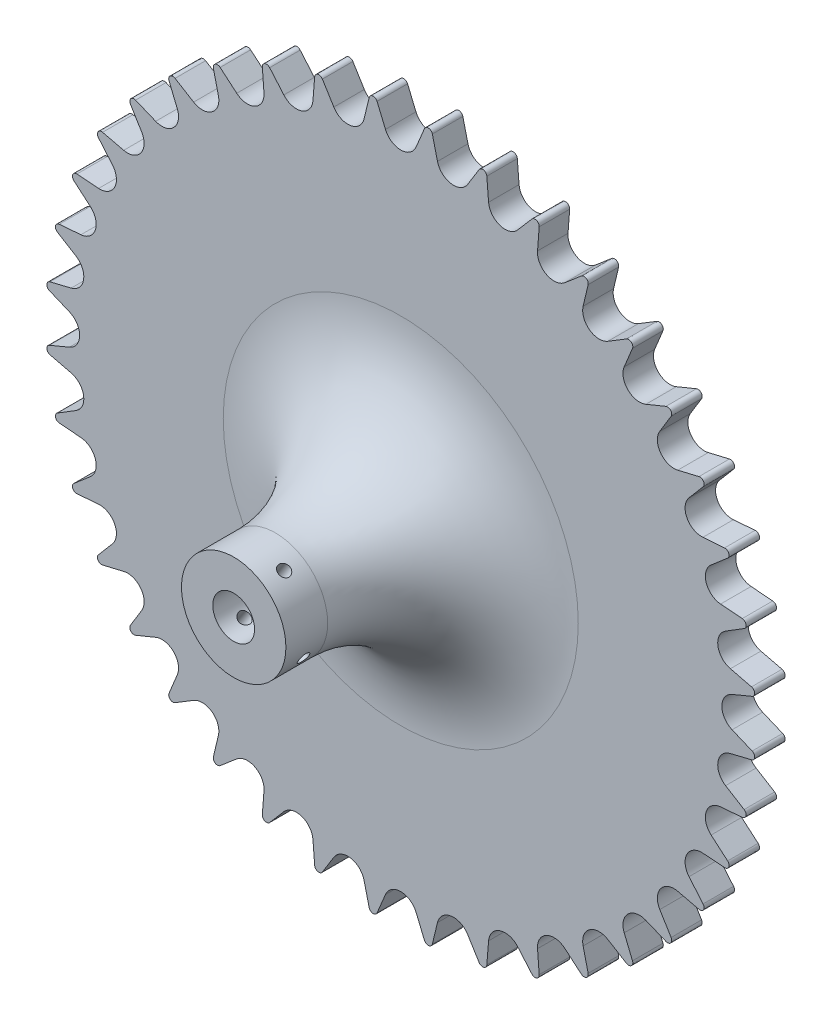
SolidWorks part; units mm, degrees
ref_plane "Front Plane" through (0, 0, 0) normal (0, 0, 1) x (1, 0, 0)
ref_plane "Top Plane" through (0, 0, 0) normal (0, 1, 0) x (1, 0, 0)
ref_plane "Right Plane" through (0, 0, 0) normal (1, 0, 0) x (0, 0, -1)
sketch "Sketch1" plane through (0, 0, 0) normal (0, 0, 1) x (1, 0, 0)
  line L0 (3.6626, 79.3215) -> (5.6677, 84.1262)
  line L1 (3.6626, 79.3215) -> (8.7911, 78.9179) construction
  line L2 (7.5623, 83.9771) -> (8.7911, 78.9179)
  line L3 (3.6626, 79.3215) -> (0, 0) construction
  line L4 (0, 0) -> (8.7911, 78.9179) construction
  line L5 (16.0261, 77.772) -> (18.7582, 82.2038)
  line L6 (20.6061, 81.7602) -> (21.0283, 76.5711)
  line L7 (27.995, 74.3074) -> (31.3867, 78.2573)
  line L8 (33.1425, 77.5301) -> (32.7478, 72.3388)
  line L9 (39.2746, 69.0132) -> (43.2424, 72.3839)
  line L10 (44.8629, 71.3909) -> (43.6609, 66.3253)
  line L11 (49.5871, 62.0196) -> (54.0334, 64.7281)
  line L12 (55.4785, 63.4939) -> (53.4989, 58.6786)
  line L13 (58.6786, 53.4989) -> (63.4939, 55.4785)
  line L14 (64.7281, 54.0334) -> (62.0196, 49.5871)
  line L15 (66.3253, 43.6609) -> (71.3909, 44.8629)
  line L16 (72.3839, 43.2424) -> (69.0132, 39.2746)
  line L17 (72.3388, 32.7478) -> (77.5301, 33.1425)
  line L18 (78.2573, 31.3867) -> (74.3074, 27.995)
  line L19 (76.5711, 21.0283) -> (81.7602, 20.6061)
  line L20 (82.2038, 18.7582) -> (77.772, 16.0261)
  line L21 (78.9179, 8.7911) -> (83.9771, 7.5623)
  line L22 (84.1262, 5.6677) -> (79.3215, 3.6626)
  line L23 (79.3215, -3.6626) -> (84.1262, -5.6677)
  line L24 (83.9771, -7.5623) -> (78.9179, -8.7911)
  line L25 (77.772, -16.0261) -> (82.2038, -18.7582)
  line L26 (81.7602, -20.6061) -> (76.5711, -21.0283)
  line L27 (74.3074, -27.995) -> (78.2573, -31.3867)
  line L28 (77.5301, -33.1425) -> (72.3388, -32.7478)
  line L29 (69.0132, -39.2746) -> (72.3839, -43.2424)
  line L30 (71.3909, -44.8629) -> (66.3253, -43.6609)
  line L31 (62.0196, -49.5871) -> (64.7281, -54.0334)
  line L32 (63.4939, -55.4785) -> (58.6786, -53.4989)
  line L33 (53.4989, -58.6786) -> (55.4785, -63.4939)
  line L34 (54.0334, -64.7281) -> (49.5871, -62.0196)
  line L35 (43.6609, -66.3253) -> (44.8629, -71.3909)
  line L36 (43.2424, -72.3839) -> (39.2746, -69.0132)
  line L37 (32.7478, -72.3388) -> (33.1425, -77.5301)
  line L38 (31.3867, -78.2573) -> (27.995, -74.3074)
  line L39 (21.0283, -76.5711) -> (20.6061, -81.7602)
  line L40 (18.7582, -82.2038) -> (16.0261, -77.772)
  line L41 (8.7911, -78.9179) -> (7.5623, -83.9771)
  line L42 (5.6677, -84.1262) -> (3.6626, -79.3215)
  line L43 (-3.6626, -79.3215) -> (-5.6677, -84.1262)
  line L44 (-7.5623, -83.9771) -> (-8.7911, -78.9179)
  line L45 (-16.0261, -77.772) -> (-18.7582, -82.2038)
  line L46 (-20.6061, -81.7602) -> (-21.0283, -76.5711)
  line L47 (-27.995, -74.3074) -> (-31.3867, -78.2573)
  line L48 (-33.1425, -77.5301) -> (-32.7478, -72.3388)
  line L49 (-39.2746, -69.0132) -> (-43.2424, -72.3839)
  line L50 (-44.8629, -71.3909) -> (-43.6609, -66.3253)
  line L51 (-49.5871, -62.0196) -> (-54.0334, -64.7281)
  line L52 (-55.4785, -63.4939) -> (-53.4989, -58.6786)
  line L53 (-58.6786, -53.4989) -> (-63.4939, -55.4785)
  line L54 (-64.7281, -54.0334) -> (-62.0196, -49.5871)
  line L55 (-66.3253, -43.6609) -> (-71.3909, -44.8629)
  line L56 (-72.3839, -43.2424) -> (-69.0132, -39.2746)
  line L57 (-72.3388, -32.7478) -> (-77.5301, -33.1425)
  line L58 (-78.2573, -31.3867) -> (-74.3074, -27.995)
  line L59 (-76.5711, -21.0283) -> (-81.7602, -20.6061)
  line L60 (-82.2038, -18.7582) -> (-77.772, -16.0261)
  line L61 (-78.9179, -8.7911) -> (-83.9771, -7.5623)
  line L62 (-84.1262, -5.6677) -> (-79.3215, -3.6626)
  line L63 (-79.3215, 3.6626) -> (-84.1262, 5.6677)
  line L64 (-83.9771, 7.5623) -> (-78.9179, 8.7911)
  line L65 (-77.772, 16.0261) -> (-82.2038, 18.7582)
  line L66 (-81.7602, 20.6061) -> (-76.5711, 21.0283)
  line L67 (-74.3074, 27.995) -> (-78.2573, 31.3867)
  line L68 (-77.5301, 33.1425) -> (-72.3388, 32.7478)
  line L69 (-69.0132, 39.2746) -> (-72.3839, 43.2424)
  line L70 (-71.3909, 44.8629) -> (-66.3253, 43.6609)
  line L71 (-62.0196, 49.5871) -> (-64.7281, 54.0334)
  line L72 (-63.4939, 55.4785) -> (-58.6786, 53.4989)
  line L73 (-53.4989, 58.6786) -> (-55.4785, 63.4939)
  line L74 (-54.0334, 64.7281) -> (-49.5871, 62.0196)
  line L75 (-43.6609, 66.3253) -> (-44.8629, 71.3909)
  line L76 (-43.2424, 72.3839) -> (-39.2746, 69.0132)
  line L77 (-32.7478, 72.3388) -> (-33.1425, 77.5301)
  line L78 (-31.3867, 78.2573) -> (-27.995, 74.3074)
  line L79 (-21.0283, 76.5711) -> (-20.6061, 81.7602)
  line L80 (-18.7582, 82.2038) -> (-16.0261, 77.772)
  line L81 (-8.7911, 78.9179) -> (-7.5623, 83.9771)
  line L82 (-5.6677, 84.1262) -> (-3.6626, 79.3215)
  line L83 (0, 80.85) -> (0, 0) construction
  line L84 (0, 0) -> (6.5906, 83.7411) construction
  circle A0 centre (0, 0) radius 80.85 construction
  arc A1 (-3.9676, 80.7526) -> (3.6626, 79.3215) centre (0, 80.85) ccw
  arc A2 (4.2537, 80.738) -> (8.4288, 80.4094) centre (0, 0) cw
  arc A3 (5.6677, 84.1262) -> (7.5623, 83.9771) centre (6.5906, 83.7411) cw
  arc A4 (8.7138, 80.3791) -> (16.0261, 77.772) centre (12.6477, 79.8546) ccw
  arc A5 (18.7582, 82.2038) -> (20.6061, 81.7602) centre (19.6094, 81.6791) cw
  arc A6 (21.1806, 78.0263) -> (27.995, 74.3074) centre (24.984, 76.8929) ccw
  arc A7 (31.3867, 78.2573) -> (33.1425, 77.5301) centre (32.1454, 77.6059) cw
  arc A8 (33.1258, 73.7523) -> (39.2746, 69.0132) centre (36.7051, 72.0379) ccw
  arc A9 (43.2424, 72.3839) -> (44.8629, 71.3909) centre (43.8899, 71.6218) cw
  arc A10 (44.2554, 67.6623) -> (49.5871, 62.0196) centre (47.5224, 65.409) ccw
  arc A11 (54.0334, 64.7281) -> (55.4785, 63.4939) centre (54.5536, 63.8741) cw
  arc A12 (54.2952, 59.9062) -> (58.6786, 53.4989) centre (57.1696, 57.1696) ccw
  arc A13 (63.4939, 55.4785) -> (64.7281, 54.0334) centre (63.8741, 54.5536) cw
  arc A14 (62.9981, 50.675) -> (66.3253, 43.6609) centre (65.409, 47.5224) ccw
  arc A15 (71.3909, 44.8629) -> (72.3839, 43.2424) centre (71.6218, 43.8899) cw
  arc A16 (70.1499, 40.196) -> (72.3388, 32.7478) centre (72.0379, 36.7051) ccw
  arc A17 (77.5301, 33.1425) -> (78.2573, 31.3867) centre (77.6059, 32.1454) cw
  arc A18 (75.5742, 28.7273) -> (76.5711, 21.0283) centre (76.8929, 24.984) ccw
  arc A19 (81.7602, 20.6061) -> (82.2038, 18.7582) centre (81.6791, 19.6094) cw
  arc A20 (79.1377, 16.5512) -> (78.9179, 8.7911) centre (79.8546, 12.6477) ccw
  arc A21 (83.9771, 7.5623) -> (84.1262, 5.6677) centre (83.7411, 6.5906) cw
  arc A22 (80.7526, 3.9676) -> (79.3215, -3.6626) centre (80.85, 0) ccw
  arc A23 (84.1262, -5.6677) -> (83.9771, -7.5623) centre (83.7411, -6.5906) cw
  arc A24 (80.3791, -8.7138) -> (77.772, -16.0261) centre (79.8546, -12.6477) ccw
  arc A25 (82.2038, -18.7582) -> (81.7602, -20.6061) centre (81.6791, -19.6094) cw
  arc A26 (78.0263, -21.1806) -> (74.3074, -27.995) centre (76.8929, -24.984) ccw
  arc A27 (78.2573, -31.3867) -> (77.5301, -33.1425) centre (77.6059, -32.1454) cw
  arc A28 (73.7523, -33.1258) -> (69.0132, -39.2746) centre (72.0379, -36.7051) ccw
  arc A29 (72.3839, -43.2424) -> (71.3909, -44.8629) centre (71.6218, -43.8899) cw
  arc A30 (67.6623, -44.2554) -> (62.0196, -49.5871) centre (65.409, -47.5224) ccw
  arc A31 (64.7281, -54.0334) -> (63.4939, -55.4785) centre (63.8741, -54.5536) cw
  arc A32 (59.9062, -54.2952) -> (53.4989, -58.6786) centre (57.1696, -57.1696) ccw
  arc A33 (55.4785, -63.4939) -> (54.0334, -64.7281) centre (54.5536, -63.8741) cw
  arc A34 (50.675, -62.9981) -> (43.6609, -66.3253) centre (47.5224, -65.409) ccw
  arc A35 (44.8629, -71.3909) -> (43.2424, -72.3839) centre (43.8899, -71.6218) cw
  arc A36 (40.196, -70.1499) -> (32.7478, -72.3388) centre (36.7051, -72.0379) ccw
  arc A37 (33.1425, -77.5301) -> (31.3867, -78.2573) centre (32.1454, -77.6059) cw
  arc A38 (28.7273, -75.5742) -> (21.0283, -76.5711) centre (24.984, -76.8929) ccw
  arc A39 (20.6061, -81.7602) -> (18.7582, -82.2038) centre (19.6094, -81.6791) cw
  arc A40 (16.5512, -79.1377) -> (8.7911, -78.9179) centre (12.6477, -79.8546) ccw
  arc A41 (7.5623, -83.9771) -> (5.6677, -84.1262) centre (6.5906, -83.7411) cw
  arc A42 (3.9676, -80.7526) -> (-3.6626, -79.3215) centre (0, -80.85) ccw
  arc A43 (-5.6677, -84.1262) -> (-7.5623, -83.9771) centre (-6.5906, -83.7411) cw
  arc A44 (-8.7138, -80.3791) -> (-16.0261, -77.772) centre (-12.6477, -79.8546) ccw
  arc A45 (-18.7582, -82.2038) -> (-20.6061, -81.7602) centre (-19.6094, -81.6791) cw
  arc A46 (-21.1806, -78.0263) -> (-27.995, -74.3074) centre (-24.984, -76.8929) ccw
  arc A47 (-31.3867, -78.2573) -> (-33.1425, -77.5301) centre (-32.1454, -77.6059) cw
  arc A48 (-33.1258, -73.7523) -> (-39.2746, -69.0132) centre (-36.7051, -72.0379) ccw
  arc A49 (-43.2424, -72.3839) -> (-44.8629, -71.3909) centre (-43.8899, -71.6218) cw
  arc A50 (-44.2554, -67.6623) -> (-49.5871, -62.0196) centre (-47.5224, -65.409) ccw
  arc A51 (-54.0334, -64.7281) -> (-55.4785, -63.4939) centre (-54.5536, -63.8741) cw
  arc A52 (-54.2952, -59.9062) -> (-58.6786, -53.4989) centre (-57.1696, -57.1696) ccw
  arc A53 (-63.4939, -55.4785) -> (-64.7281, -54.0334) centre (-63.8741, -54.5536) cw
  arc A54 (-62.9981, -50.675) -> (-66.3253, -43.6609) centre (-65.409, -47.5224) ccw
  arc A55 (-71.3909, -44.8629) -> (-72.3839, -43.2424) centre (-71.6218, -43.8899) cw
  arc A56 (-70.1499, -40.196) -> (-72.3388, -32.7478) centre (-72.0379, -36.7051) ccw
  arc A57 (-77.5301, -33.1425) -> (-78.2573, -31.3867) centre (-77.6059, -32.1454) cw
  arc A58 (-75.5742, -28.7273) -> (-76.5711, -21.0283) centre (-76.8929, -24.984) ccw
  arc A59 (-81.7602, -20.6061) -> (-82.2038, -18.7582) centre (-81.6791, -19.6094) cw
  arc A60 (-79.1377, -16.5512) -> (-78.9179, -8.7911) centre (-79.8546, -12.6477) ccw
  arc A61 (-83.9771, -7.5623) -> (-84.1262, -5.6677) centre (-83.7411, -6.5906) cw
  arc A62 (-80.7526, -3.9676) -> (-79.3215, 3.6626) centre (-80.85, 0) ccw
  arc A63 (-84.1262, 5.6677) -> (-83.9771, 7.5623) centre (-83.7411, 6.5906) cw
  arc A64 (-80.3791, 8.7138) -> (-77.772, 16.0261) centre (-79.8546, 12.6477) ccw
  arc A65 (-82.2038, 18.7582) -> (-81.7602, 20.6061) centre (-81.6791, 19.6094) cw
  arc A66 (-78.0263, 21.1806) -> (-74.3074, 27.995) centre (-76.8929, 24.984) ccw
  arc A67 (-78.2573, 31.3867) -> (-77.5301, 33.1425) centre (-77.6059, 32.1454) cw
  arc A68 (-73.7523, 33.1258) -> (-69.0132, 39.2746) centre (-72.0379, 36.7051) ccw
  arc A69 (-72.3839, 43.2424) -> (-71.3909, 44.8629) centre (-71.6218, 43.8899) cw
  arc A70 (-67.6623, 44.2554) -> (-62.0196, 49.5871) centre (-65.409, 47.5224) ccw
  arc A71 (-64.7281, 54.0334) -> (-63.4939, 55.4785) centre (-63.8741, 54.5536) cw
  arc A72 (-59.9062, 54.2952) -> (-53.4989, 58.6786) centre (-57.1696, 57.1696) ccw
  arc A73 (-55.4785, 63.4939) -> (-54.0334, 64.7281) centre (-54.5536, 63.8741) cw
  arc A74 (-50.675, 62.9981) -> (-43.6609, 66.3253) centre (-47.5224, 65.409) ccw
  arc A75 (-44.8629, 71.3909) -> (-43.2424, 72.3839) centre (-43.8899, 71.6218) cw
  arc A76 (-40.196, 70.1499) -> (-32.7478, 72.3388) centre (-36.7051, 72.0379) ccw
  arc A77 (-33.1425, 77.5301) -> (-31.3867, 78.2573) centre (-32.1454, 77.6059) cw
  arc A78 (-28.7273, 75.5742) -> (-21.0283, 76.5711) centre (-24.984, 76.8929) ccw
  arc A79 (-20.6061, 81.7602) -> (-18.7582, 82.2038) centre (-19.6094, 81.6791) cw
  arc A80 (-16.5512, 79.1377) -> (-8.7911, 78.9179) centre (-12.6477, 79.8546) ccw
  arc A81 (-7.5623, 83.9771) -> (-5.6677, 84.1262) centre (-6.5906, 83.7411) cw
  point P13 (41.8082, 75.9997)
  point P14 (0, 0)
  point P289 (0, 0)
  dimension "D1" = 161.7
  dimension "D2" = 3.9688
  dimension "D5" = 1
  dimension "D6" = 84
  dimension "D3" = 4.5
  dimension "D4" = 40
extrude "Boss-Extrude1" add sketch "Sketch1" along normal blind 7.3 contours A81 L81 A80 L80 A79 L79 A78 L78 A77 L77 A76 L76 A75 L75 A74 L74 A73 L73 A72 L72 A71 L71 A70 L70 A69 L69 A68 L68 A67 L67 A66 L66 A65 L65 A64 L64 A63 L63 A62 L62 A61 L61 A60 L60 A59 L59 A58 L58 A57 L57 A56 | A3 L0 A2 L2 region at (-0.0037, -0.0473, 0) region at (6.4765, 82.2915, 0)
sketch "Sketch2" plane through (0, 0, 7.3) normal (0, 0, 1) x (1, 0, 0)
  circle A0 centre (0, 0) radius 12.5
  dimension "D1" = 25
extrude "Boss-Extrude2" add sketch "Sketch2" along normal blind 40
fillet "Fillet1" radius 30 1 edges at (12.5, 0, 7.3)
sketch "Sketch3" plane through (0, 0, 47.3) normal (0, 0, 1) x (1, 0, 0)
  circle A0 centre (0, 0) radius 5
  dimension "D1" = 10
extrude "Cut-Extrude1" cut sketch "Sketch3" against normal through all
hole_wizard "Ø1.0mm Dowel Hole1" positions "3DSketch1" profile "Sketch4" hole size "Ø1.0" standard "ANSI Metric"
sketch3d "3DSketch1"
  point P0 (-6.8176, -10.4771, 42.0201)
  point P2 (-11.0684, 5.8086, 41.6583)
sketch "Sketch4" plane through (-6.8176, -10.4771, 42.0201) normal (0, 0, 1) x (0.8382, -0.5454, 0)
  line L0 (0, 0) -> (0, 34)
  line L1 (0, 34) -> (1.4, 33.1588)
  line L2 (1.4, 33.1588) -> (1.4, 0)
  line L5 (1.4, 0) -> (0, 0)
  line L10 (0, 34) -> (-1.4, 33.1588) construction
  line L11 (0, -6.35) -> (0, 107.95) construction
  dimension "Hole Dia." = 2.8
  dimension "Hole Depth" = 34
  dimension "Drill Angle" = 118
